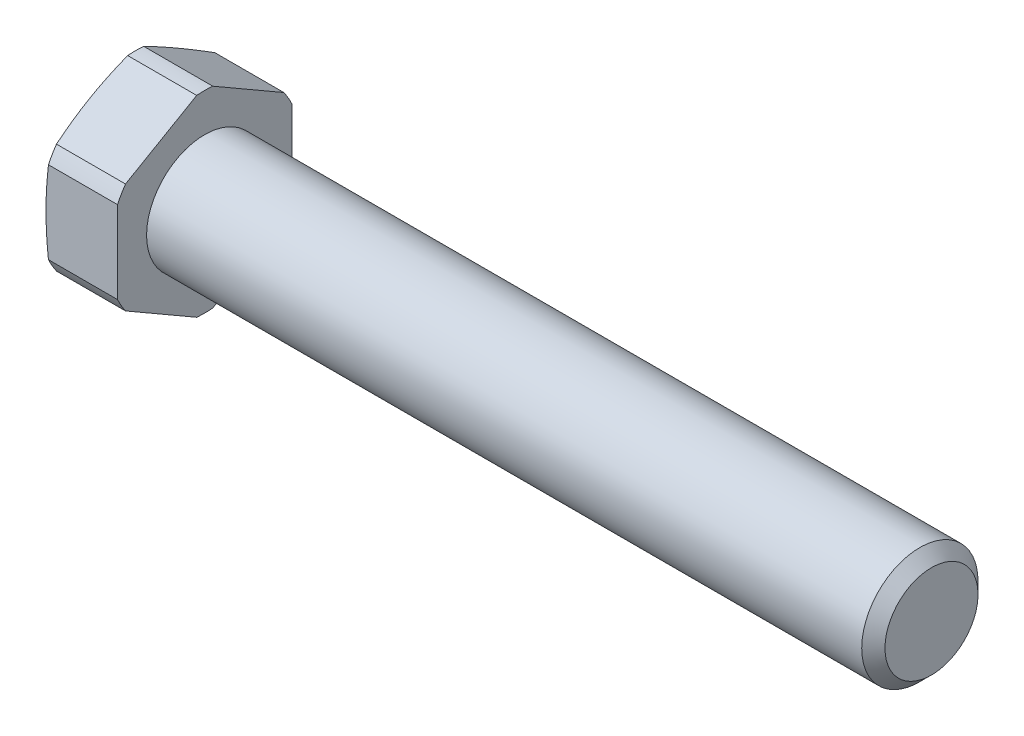
SolidWorks part; units mm, degrees
material "AISI 1020"
ref_plane "Спереди" through (0, 0, 0) normal (0, 0, 1) x (1, 0, 0)
ref_plane "Сверху" through (0, 0, 0) normal (0, 1, 0) x (1, 0, 0)
ref_plane "Справа" through (0, 0, 0) normal (1, 0, 0) x (0, 0, -1)
sketch "Эскиз1" plane through (0, 0, 0) normal (0, 0, 1) x (1, 0, 0)
  line L0 (-1000, 0) -> (49000, 0) construction
  line L1 (-7.5, 0) -> (-7.5, 8.55)
  line L2 (-7.5, 8.55) -> (-7.1249, 9.95)
  line L3 (-7.1249, 9.95) -> (0, 9.95)
  line L4 (0, 9.95) -> (0, 6)
  line L5 (0, 6) -> (73.8, 6)
  line L6 (75, 4.8) -> (75, 0)
  line L7 (75, 6) -> (75.875, 7.5155) construction
  line L8 (75.875, 7.5155) -> (76.75, 6) construction
  line L9 (76.75, 6) -> (75, 6) construction
  line L10 (75.875, 7.5155) -> (75.875, 6) construction
  line L11 (75.875, 7.5155) -> (45.875, 7.5155) construction
  line L12 (73.8, 6) -> (75, 4.8)
  line L13 (75, 6) -> (74.4, 5.4) construction
  line L14 (-7.5, 8.55) -> (-25.5, 8.55) construction
  line L15 (-7.5, 0) -> (75, 0)
  dimension "D1" = 1.2
  dimension "D2" = 15
revolve "Повернуть1" add sketch "Эскиз1" angle 360 about L0
cosmetic thread "Условное изображение резьбы1" parameters "D1"=30, "D2"=8.9689
sketch "Эскиз2" plane through (-7.5, 0, 0) normal (-1, 0, 0) x (0, 0, 1)
  line L1 (0, 10.3923) -> (-9, 5.1962)
  line L2 (-9, 5.1962) -> (-9, -5.1962)
  line L3 (-9, -5.1962) -> (0, -10.3923)
  line L4 (0, -10.3923) -> (9, -5.1962)
  line L5 (9, -5.1962) -> (9, 5.1962)
  line L6 (9, 5.1962) -> (0, 10.3923)
  circle A0 centre (0, 0) radius 9 construction
  dimension "D1" = 18
extrude "Вырез-Вытянуть1" cut sketch "Эскиз2" against normal up to surface (82.5 mm away) flip side to cut up to face at (75, 0, 4.8)
equation "\"D1@Эскиз1\"=\"_d_@Эскиз1\"/10"
equation "\"D@Эскиз1\"=\"S_@Эскиз1\"*0.95"
equation "\"D1@Эскиз2\"=\"S_@Эскиз1\""
equation "\"D1@Условное изображение резьбы1\"=\"b_@Эскиз1\""
equation "\"D2@Условное изображение резьбы1\"=\"_d_@Эскиз1\"-\"dr@Эскиз1\"*2"
